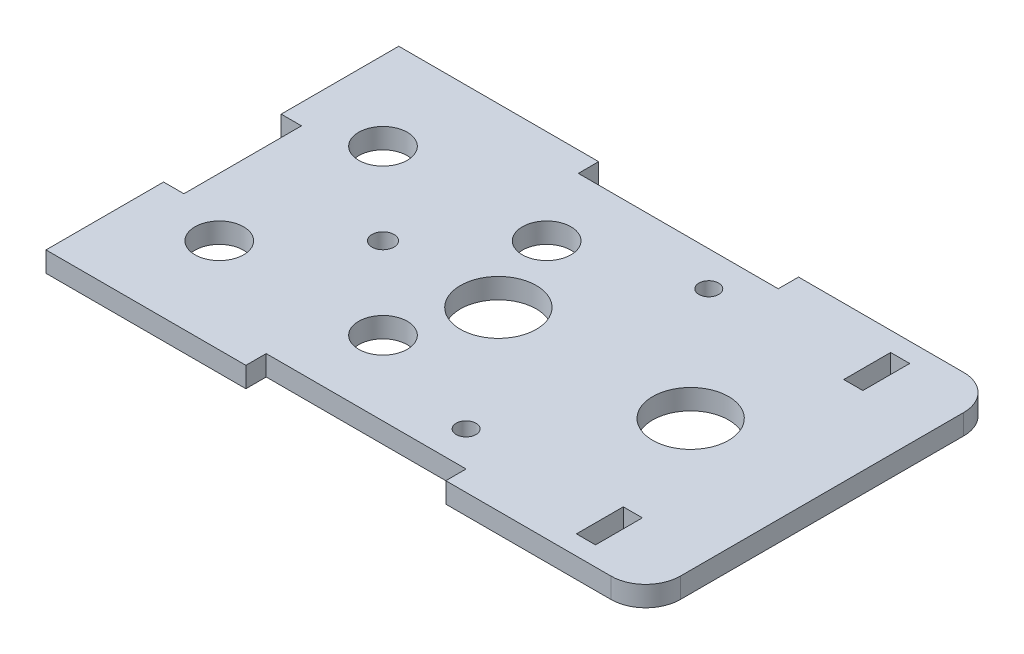
SolidWorks part; units mm, degrees
ref_plane "Front Plane" through (0, 0, 0) normal (0, 0, 1) x (1, 0, 0)
ref_plane "Top Plane" through (0, 0, 0) normal (0, 1, 0) x (1, 0, 0)
ref_plane "Right Plane" through (0, 0, 0) normal (1, 0, 0) x (0, 0, -1)
sketch "Sketch1" plane through (0, 0, 0) normal (0, 1, 0) x (1, 0, 0)
  line L1 (-86.36, -50.8) -> (86.36, -50.8)
  line L2 (-86.36, -50.8) -> (-86.36, 50.8)
  line L3 (-86.36, 50.8) -> (86.36, 50.8)
  line L4 (86.36, -50.8) -> (86.36, 50.8)
  line L5 (-86.36, -50.8) -> (86.36, 50.8) construction
  line L6 (-86.36, 50.8) -> (86.36, -50.8) construction
  point P0 (0, 0)
  dimension "D1" = 172.72
  dimension "D2" = 101.6
extrude "Boss-Extrude1" add sketch "Sketch1" along normal blind 5.85
sketch "Sketch2" plane through (0, 0, 0) normal (0, 1, 0) x (1, 0, 0)
  line L0 (-86.36, 0) -> (0, 0) construction
  line L2 (0, 0) -> (86.36, 0) construction
  line L4 (0, 50.8) -> (0, -50.8) construction
  line L7 (-6.8721, 0) -> (-40.1037, 0) construction
  line L8 (48.5139, 0) -> (-6.8721, 0) construction
  line L9 (-86.36, 50.8) -> (-86.36, -50.8) construction
  line L10 (86.36, -50.8) -> (86.36, 50.8) construction
  line L11 (-40.1037, 0) -> (-6.8721, 0) construction
  line L21 (-63.6769, -23.5732) -> (-16.5306, -23.5732) construction
  line L22 (-63.6769, -23.5732) -> (-63.6769, 23.5732) construction
  line L23 (-63.6769, 23.5732) -> (-16.5306, 23.5732) construction
  line L24 (-16.5306, -23.5732) -> (-16.5306, 23.5732) construction
  line L25 (-63.6769, -23.5732) -> (-16.5306, 23.5732) construction
  line L26 (-63.6769, 23.5732) -> (-16.5306, -23.5732) construction
  line L29 (26.7151, -50.8) -> (26.7151, 50.8) construction
  line L30 (-63.6769, 23.5732) -> (-63.6769, 30.5732) construction
  circle A1 centre (-6.8721, 0) radius 10.935
  circle A2 centre (-40.1037, 0) radius 3.175
  circle A3 centre (-63.6769, 23.5732) radius 7
  circle A4 centre (-16.5306, 23.5732) radius 7
  circle A5 centre (-63.6769, -23.5732) radius 7
  circle A6 centre (-16.5306, -23.5732) radius 7
  circle A7 centre (48.5139, 0) radius 10.935
  dimension "D1" = 6.35
  dimension "D2" = 14
  dimension "D3" = 14
  dimension "D4" = 14
  dimension "D8" = 14
  dimension "D9" = 21.87
  dimension "D10" = 21.87
  dimension "D5" = 55.386
  dimension "D6" = 33.2317
  dimension "D7" = 46.2563
extrude "Cut-Extrude4" cut sketch "Sketch2" along normal blind 10
sketch "Sketch4" plane through (0, 5.85, 0) normal (0, 1, 0) x (1, 0, 0)
  line L0 (-86.36, 50.8) -> (-86.36, -50.8) construction
  line L1 (-86.36, 16.9333) -> (-80.51, 16.9333)
  line L2 (-86.36, 16.9333) -> (-86.36, -16.9333)
  line L3 (-86.36, -16.9333) -> (-80.51, -16.9333)
  line L4 (-80.51, 16.9333) -> (-80.51, -16.9333)
  line L5 (-86.36, -50.8) -> (86.36, -50.8) construction
  line L6 (-28.7867, -50.8) -> (28.7867, -50.8)
  line L7 (-28.7867, -50.8) -> (-28.7867, -44.95)
  line L8 (-28.7867, -44.95) -> (28.7867, -44.95)
  line L9 (28.7867, -50.8) -> (28.7867, -44.95)
  line L10 (86.36, 50.8) -> (-86.36, 50.8) construction
  line L11 (-28.7867, 50.8) -> (28.7867, 50.8)
  line L12 (-28.7867, 50.8) -> (-28.7867, 44.95)
  line L13 (-28.7867, 44.95) -> (28.7867, 44.95)
  line L14 (28.7867, 50.8) -> (28.7867, 44.95)
  line L15 (-28.7867, 44.95) -> (-28.7867, -44.95) construction
  line L16 (28.7867, 44.95) -> (28.7867, -44.95) construction
  line L17 (60.86, 31.75) -> (60.86, -31.75) construction
  line L18 (60.86, -31.75) -> (66.36, -31.75)
  line L19 (60.86, -31.75) -> (60.86, -45.25)
  line L20 (60.86, -45.25) -> (66.36, -45.25)
  line L21 (66.36, -31.75) -> (66.36, -45.25)
  line L22 (60.86, 45.25) -> (66.36, 45.25)
  line L23 (60.86, 45.25) -> (60.86, 31.75)
  line L24 (60.86, 31.75) -> (66.36, 31.75)
  line L25 (66.36, 45.25) -> (66.36, 31.75)
  line L26 (66.36, 31.75) -> (66.36, -31.75) construction
  line L27 (86.36, -50.8) -> (86.36, 50.8) construction
  dimension "D1" = 5.85
  dimension "D2" = 5.85
  dimension "D3" = 5.85
  dimension "D4" = 57.5733
  dimension "D5" = 57.5733
  dimension "D6" = 33.8667
  dimension "D7" = 33.8667
  dimension "D8" = 5.55
  dimension "D9" = 5.55
  dimension "D10" = 5.5
  dimension "D11" = 13.5
  dimension "D12" = 13.5
  dimension "D13" = 20
extrude "Cut-Extrude5" cut sketch "Sketch4" against normal blind 10
fillet "Fillet1" radius 10 1 edges at (86.36, 2.925, -50.8)
fillet "Fillet2" radius 10 1 edges at (86.36, 2.925, 50.8)
sketch "Sketch5" plane through (0, 5.85, 0) normal (0, 1, 0) x (1, 0, 0)
  line L0 (28.7867, -44.95) -> (28.7867, -34.95) construction
  line L1 (28.7867, -34.95) -> (18.7867, -34.95) construction
  line L2 (28.7867, 44.95) -> (28.7867, 34.95) construction
  line L3 (28.7867, 34.95) -> (18.7867, 34.95) construction
  circle A0 centre (18.7867, -34.95) radius 2.85
  circle A1 centre (18.7867, 34.95) radius 2.85
  dimension "D3" = 5.7
  dimension "D4" = 5.7
  dimension "D1" = 10
  dimension "D2" = 10
  dimension "D5" = 10
  dimension "D6" = 10
extrude "Cut-Extrude6" cut sketch "Sketch5" against normal blind 10
equation "\"D1@Sketch1\" = \"Length@RudderBox.SLDASM\""
equation "\"D2@Sketch1\" = \"Width@RudderBox.SLDASM\""
equation "\"D1@Boss-Extrude1\" = \"Material@RudderBox.SLDASM\""
equation "\"D1@Sketch4\" = \"Material@RudderBox.SLDASM\""
equation "\"D2@Sketch4\" = \"Material@RudderBox.SLDASM\""
equation "\"D3@Sketch4\" = \"Material@RudderBox.SLDASM\""
equation "\"D4@Sketch4\" = \"Length@RudderBox.SLDASM\"/3"
equation "\"D5@Sketch4\" = \"Length@RudderBox.SLDASM\"/3"
equation "\"D6@Sketch4\" = \"Width@RudderBox.SLDASM\"/3"
equation "\"D7@Sketch4\" = \"Width@RudderBox.SLDASM\"/3"
